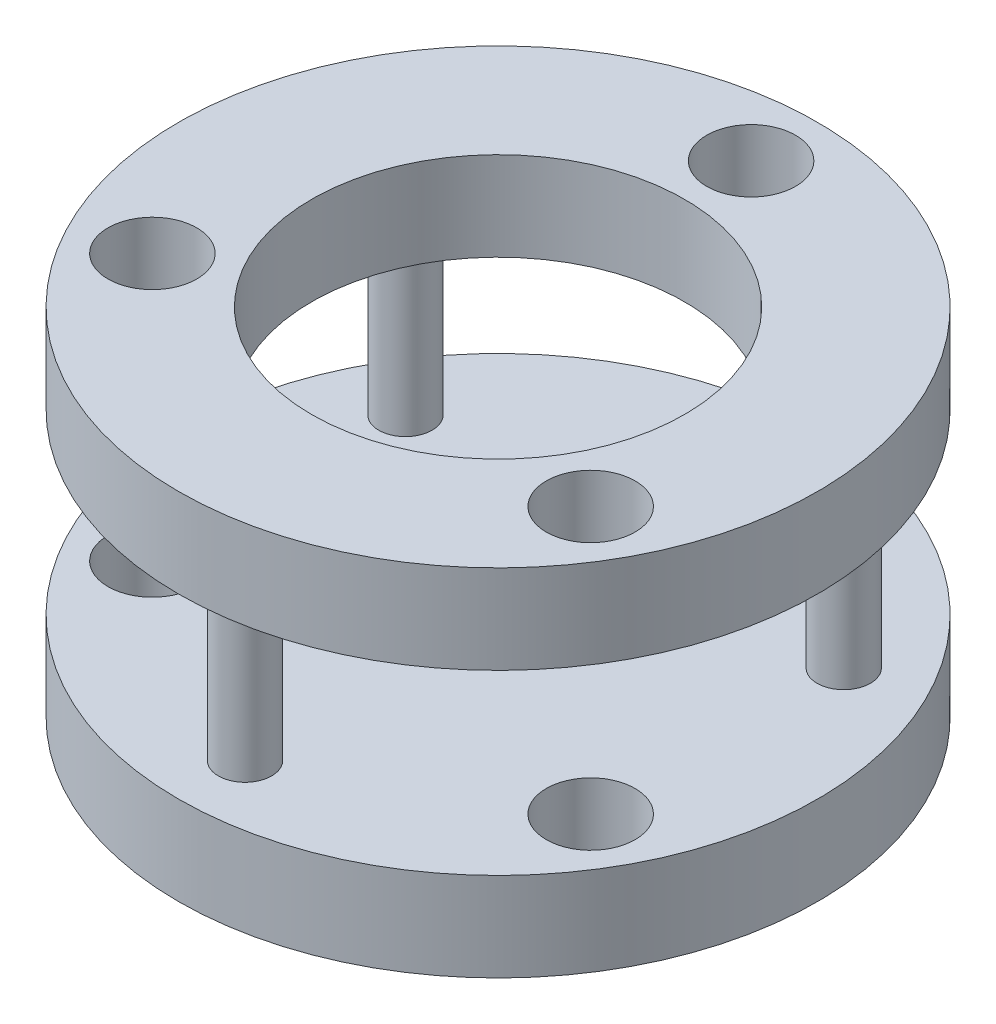
SolidWorks part; units mm, degrees
ref_plane "Front Plane" through (0, 0, 0) normal (0, 0, 1) x (1, 0, 0)
ref_plane "Top Plane" through (0, 0, 0) normal (0, 1, 0) x (1, 0, 0)
ref_plane "Right Plane" through (0, 0, 0) normal (1, 0, 0) x (0, 0, -1)
sketch "Sketch1" plane through (0, 0, 0) normal (0, 1, 0) x (1, 0, 0)
  line L0 (0, 0) -> (0, 28.5) construction
  line L1 (0, 0) -> (24.6817, -14.25) construction
  line L2 (0, 0) -> (-24.6817, -14.25) construction
  circle A0 centre (0, 0) radius 48.5
  circle A1 centre (0, 28.5) radius 5
  circle A2 centre (0, 28.5) radius 20 construction
  circle A3 centre (24.6817, -14.25) radius 20 construction
  circle A4 centre (24.6817, -14.25) radius 5
  circle A5 centre (-24.6817, -14.25) radius 20 construction
  circle A6 centre (-24.6817, -14.25) radius 5
  circle A7 centre (0, 0) radius 28.5
  circle A8 centre (0, 0) radius 21
  circle A9 centre (0, 0) radius 36
  circle A10 centre (0, -28.5) radius 3
  circle A11 centre (-24.6817, 14.25) radius 3
  circle A12 centre (24.6817, 14.25) radius 3
  point P16 (0, 0)
  point P20 (0, 0)
  point P21 (0, 0)
  point P22 (0, 0)
  point P27 (0, 0)
  point P28 (0, 0)
  dimension "D1" = 97
  dimension "D4" = 10
  dimension "D5" = 3
  dimension "D9" = 40
  dimension "D10" = 6
  dimension "D2" = 120
  dimension "D3" = 120
  dimension "D7" = 7.5
  dimension "D8" = 7.5
  dimension "D6" = 3
extrude "Boss-Extrude1" add sketch "Sketch1" along normal blind 10 contours A9 A7 A4 A6 A1 | A4 A7 A1 A6 A8 region at (0, 0, -22.6981) region at (-34.9818, 0, 0)
extrude "Boss-Extrude2" add sketch "Sketch1<3>" along normal blind 40 contours A10 | A11 | A12
sketch "Sketch1<3>" plane through (0, 0, 0) normal (0, 1, 0) x (1, 0, 0) same geometry as "Sketch1"
pattern_linear "LPattern3" count 2 spacing 30 along (0, 1, 0) of "Boss-Extrude1"
sketch "Sketch2" plane through (0, 0, 0) normal (0, -1, 0) x (1, 0, 0)
  circle A0 centre (0, 0) radius 21 construction
  circle A1 centre (0, 0) radius 21
extrude "Boss-Extrude3" add sketch "Sketch2" against normal blind 10
sketch "Sketch4" plane through (0, 0, 0) normal (0, -1, 0) x (1, 0, 0)
  circle A0 centre (0, 0) radius 5
  dimension "D1" = 10
extrude "Boss-Extrude4" add sketch "Sketch4" along normal blind 20
fillet "Fillet1" radius 10 1 edges at (0, 0, 5)
